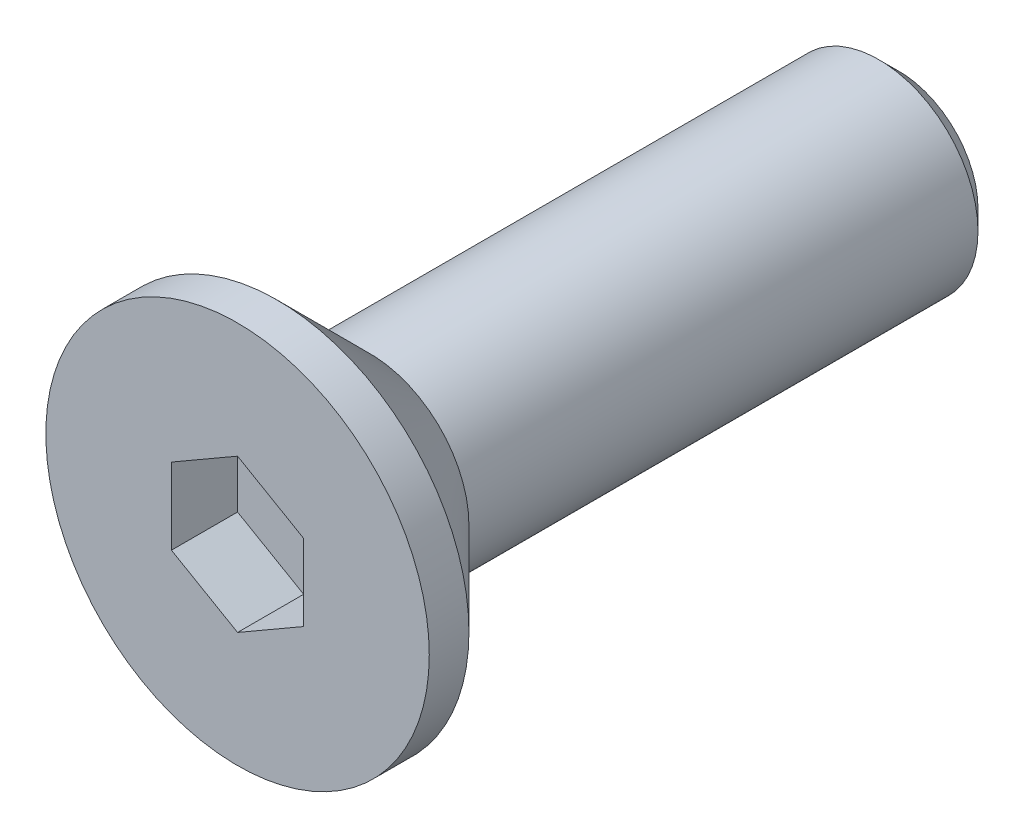
SolidWorks part; units mm, degrees
material "1.4000 (X6Cr13)"
ref_plane "Ebene vorne" through (0, 0, 0) normal (0, 0, 1) x (1, 0, 0)
ref_plane "Ebene oben" through (0, 0, 0) normal (0, 1, 0) x (1, 0, 0)
ref_plane "Ebene rechts" through (0, 0, 0) normal (1, 0, 0) x (0, 0, -1)
sketch "Skizze1" plane through (0, 0, 0) normal (1, 0, 0) x (0, 0, -1)
  line L0 (-31.7636, 0) -> (42.9935, 0) construction
  line L1 (0, 26.0256) -> (0, -29.3045) construction
  line L2 (0, 0) -> (0, 2.9)
  line L3 (0.6, 2.9) -> (2, 1.5)
  line L4 (2, 1.5) -> (10, 1.5)
  line L5 (10, 1.5) -> (10, 0)
  line L6 (10, 0) -> (0, 0)
  line L7 (0, 2.9) -> (0.6, 2.9)
  dimension "D1" = 3
  dimension "D2" = 10
  dimension "D3" = 5.8
  dimension "D4" = 45
  dimension "D5" = 2
  dimension "D6" = 0.6
revolve "Rotation1" add sketch "Skizze1" angle 360 about L0
sketch "Skizze3" plane through (0, 0, 0) normal (0, 0, 1) x (1, 0, 0)
  line L0 (0, 1.5356) -> (0, -1.3958) construction
  line L1 (-1.5297, 0) -> (1.3792, 0) construction
  line L3 (1, -0.5774) -> (1, 0.5774)
  line L4 (1, 0.5774) -> (0, 1.1547)
  line L5 (0, 1.1547) -> (-1, 0.5774)
  line L6 (-1, 0.5774) -> (-1, -0.5774)
  line L7 (-1, -0.5774) -> (0, -1.1547)
  line L8 (0, -1.1547) -> (1, -0.5774)
  circle A0 centre (0, 0) radius 1 construction
  dimension "D1" = 2
extrude "Schnitt-Linear austragen1" cut sketch "Skizze3" against normal blind 1
chamfer "Fase1" distance 0.3 angle 45 1 edges at (1.5, 0, -10)
ref_axis "Achse1" through (0, 0, 0.5) along (0, 0, -1)
